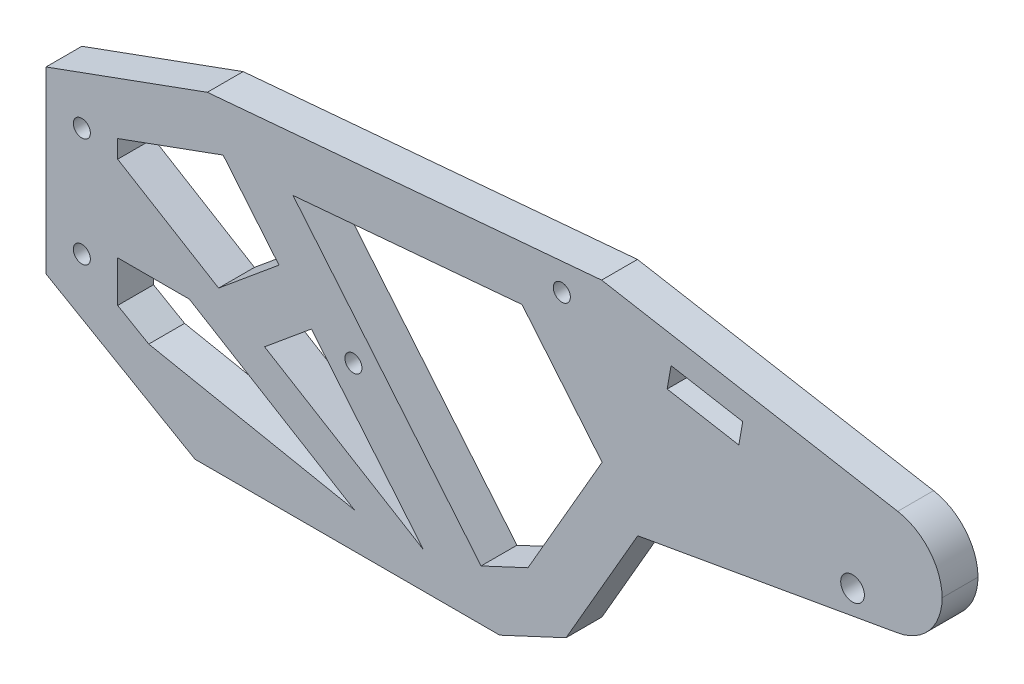
SolidWorks part; units mm, degrees
ref_plane "Plan de face" through (0, 0, 0) normal (0, 0, 1) x (1, 0, 0)
ref_plane "Plan de dessus" through (0, 0, 0) normal (0, 1, 0) x (1, 0, 0)
ref_plane "Plan de droite" through (0, 0, 0) normal (1, 0, 0) x (0, 0, -1)
sketch "Esquisse1" plane through (0, 0, 0) normal (0, 0, 1) x (1, 0, 0)
  line L1 (0, 0) -> (250, 0)
  line L2 (0, 0) -> (0, 100)
  line L3 (0, 100) -> (250, 100)
  line L4 (250, 0) -> (250, 100)
  dimension "D1" = 100
  dimension "D2" = 250
extrude "Boss.-Extru.1" add sketch "Esquisse1" along normal blind 10 contours L3 L4 L1 L2
sketch "Esquisse2" plane through (0, 0, 10) normal (0, 0, 1) x (1, 0, 0)
  line L0 (250, 83.2489) -> (155, 100)
  line L1 (250, 0) -> (250, 100) construction
  line L2 (0, 100) -> (250, 100) construction
  line L3 (155, 100) -> (45, 90.3762)
  line L4 (45, 90.3762) -> (0, 73.9976)
  line L5 (0, 0) -> (0, 100) construction
  line L6 (0, 73.9976) -> (0, 23.9976)
  line L7 (0, 23.9976) -> (41.565, 0)
  line L8 (0, 0) -> (250, 0) construction
  line L9 (41.565, 0) -> (126.565, 0)
  line L10 (126.565, 0) -> (145.0819, 8.6346)
  line L11 (145.0819, 8.6346) -> (165.0819, 43.2756)
  line L12 (165.0819, 43.2756) -> (250, 58.2489)
  line L13 (250, 58.2489) -> (250, 83.2489)
  dimension "D1" = 10
  dimension "D2" = 10
  dimension "D3" = 25
  dimension "D4" = 30
  dimension "D5" = 15
  dimension "D6" = 5
  dimension "D7" = 25
  dimension "D8" = 50
  dimension "D9" = 45
  dimension "D10" = 95
  dimension "D11" = 20
  dimension "D12" = 85
extrude "Enlèv. mat.-Extru.1" cut sketch "Esquisse2" against normal through all flip side to cut
sketch "Esquisse3" plane through (0, 0, 10) normal (0, 0, 1) x (1, 0, 0)
  line L0 (134.4563, 20.2304) -> (155.1413, 56.0578)
  line L1 (155.1413, 56.0578) -> (132.8009, 83.0005)
  line L2 (132.8009, 83.0005) -> (68.9043, 77.4103)
  line L3 (68.9043, 77.4103) -> (121.3747, 14.1304)
  line L4 (105.3137, 10) -> (74.0464, 47.7088)
  line L5 (74.0464, 47.7088) -> (60.9752, 36.8705)
  line L6 (60.9752, 36.8705) -> (105.3137, 10)
  line L8 (20, 26.3753) -> (20, 37.8891)
  line L9 (20, 37.8891) -> (40, 37.8891)
  line L10 (40, 37.8891) -> (86.0193, 10)
  line L11 (20, 61.7028) -> (48.1471, 44.6448)
  line L12 (48.1471, 44.6448) -> (65, 58.6188)
  line L13 (65, 58.6188) -> (49.4185, 77.4103)
  line L14 (49.4185, 77.4103) -> (20, 66.7028)
  line L15 (20, 66.7028) -> (20, 61.7028)
  line L16 (155, 100) -> (45, 90.3762) construction
  line L17 (145.0819, 8.6346) -> (165.0819, 43.2756) construction
  line L18 (0, 23.9976) -> (41.565, 0) construction
  line L19 (126.565, 0) -> (145.0819, 8.6346) construction
  line L20 (28.6603, 21.3753) -> (86.0193, 10)
  line L21 (45, 90.3762) -> (0, 73.9976) construction
  line L22 (0, 23.9976) -> (0, 73.9976) construction
  line L23 (121.3747, 14.1304) -> (134.4563, 20.2304)
  line L24 (41.565, 0) -> (126.565, 0) construction
  line L25 (20, 26.3753) -> (28.6603, 21.3753)
  dimension "D1" = 15
  dimension "D2" = 35
  dimension "D3" = 10
  dimension "D4" = 20
  dimension "D5" = 45
  dimension "D6" = 10
  dimension "D7" = 20
  dimension "D8" = 1.217
  dimension "D9" = 15
  dimension "D10" = 5
  dimension "D11" = 15
  dimension "D12" = 15
  dimension "D13" = 20
  dimension "D14" = 15
  dimension "D15" = 10
  dimension "D16" = 20
extrude "Enlèv. mat.-Extru.2" cut sketch "Esquisse3" against normal through all
fillet "Congé1" radius 15 2 edges at (250, 83.2489, 5) (250, 58.2489, 5)
sketch "Esquisse4" plane through (0, 0, 10) normal (0, 0, 1) x (1, 0, 0)
  line L0 (224.9998, 60.5372) -> (224.9998, 87.6572) construction
  line L1 (237.6047, 85.4346) -> (155, 100) construction
  circle A0 centre (224.9998, 60.5372) radius 3.305
  dimension "D1" = 6.61
  dimension "D2" = 25
  dimension "D3" = 27.12
extrude "Enlèv. mat.-Extru.3" cut sketch "Esquisse4" against normal through all
hole_wizard "Perçage pour écrous auto-bloquants 300® #6 (SP)1" positions "Esquisse5" profile "Esquisse6" hole size "#6-32" standard "PEM® Inch" end condition through all
sketch "Esquisse5" plane through (0, 0, 10) normal (0, 0, 1) x (1, 0, 0)
  line L7 (85.764, 45.3272) -> (48.1797, 90.6544) construction
  line L8 (155, 100) -> (45, 90.3762) construction
  line L10 (85.764, 45.3272) -> (123.3484, 0) construction
  line L11 (41.565, 0) -> (126.565, 0) construction
  line L13 (68.9043, 77.4103) -> (121.3747, 14.1304) construction
  line L14 (91.5375, 50.1144) -> (85.764, 45.3272) construction
  line L15 (85.764, 45.3272) -> (79.9906, 40.54) construction
  line L16 (105.3137, 10) -> (74.0464, 47.7088) construction
  line L21 (132.8009, 83.0005) -> (143.9005, 91.5003) construction
  line L22 (143.9005, 91.5003) -> (155, 100) construction
  point P0 (85.764, 45.3272)
  point P41 (143.9005, 91.5003)
  dimension "D1" = 7.5
sketch "Esquisse6" plane through (85.764, 45.3272, 10) normal (1, 0, 0) x (0, -1, 0)
  line L0 (0, 0) -> (0, 10)
  line L1 (0, 10) -> (2.3812, 10)
  line L2 (2.3812, 10) -> (2.3812, 0)
  line L5 (2.3812, 0) -> (0, 0)
  line L11 (0, -6.35) -> (0, 107.95) construction
  dimension "Diamètre du perçage jusqu'au prochain" = 4.7625
  dimension "Profondeur du perçage jusqu'au prochain" = 10
hole_wizard "Perçage pour écrous auto-bloquants 300® #6 (SP)2" positions "Esquisse8" profile "Esquisse9" hole size "#6-32" standard "PEM® Inch" end condition through all
sketch "Esquisse8" plane through (0, 0, 10) normal (0, 0, 1) x (1, 0, 0)
  line L0 (10, 64.2028) -> (0, 64.2028) construction
  line L1 (0, 23.9976) -> (0, 73.9976) construction
  line L3 (10, 64.2028) -> (20, 64.2028) construction
  line L4 (20, 66.7028) -> (20, 61.7028) construction
  line L6 (10, 64.2028) -> (10, 33.7923) construction
  point P0 (10, 64.2028)
  point P2 (10, 33.7923)
  point P23 (0, 48.9976)
  point P24 (10, 48.9976)
  point P26 (20, 64.2028)
sketch "Esquisse9" plane through (10, 64.2028, 10) normal (1, 0, 0) x (0, -1, 0)
  line L0 (0, 0) -> (0, 10)
  line L1 (0, 10) -> (2.3812, 10)
  line L2 (2.3812, 10) -> (2.3812, 0)
  line L5 (2.3812, 0) -> (0, 0)
  line L11 (0, -6.35) -> (0, 107.95) construction
  dimension "Diamètre du perçage jusqu'au prochain" = 4.7625
  dimension "Profondeur du perçage jusqu'au prochain" = 10
sketch "Esquisse10" plane through (0, 0, 10) normal (0, 0, 1) x (1, 0, 0)
  line L0 (174.3731, 89.0292) -> (173.2791, 82.8249)
  line L1 (174.3731, 89.0292) -> (194.3647, 85.5042)
  line L2 (173.2791, 82.8249) -> (193.2707, 79.2999)
  line L3 (194.3647, 85.5042) -> (193.2707, 79.2999)
  line L4 (183.2749, 81.0624) -> (224.9998, 60.5372) construction
  line L6 (237.6047, 85.4346) -> (155, 100) construction
  dimension "D1" = 20.3
  dimension "D2" = 6.3
  dimension "D3" = 46.5
  dimension "D4" = 7.44
extrude "Enlèv. mat.-Extru.4" cut sketch "Esquisse10" against normal blind 10 contours L1 L3 L2 L0
